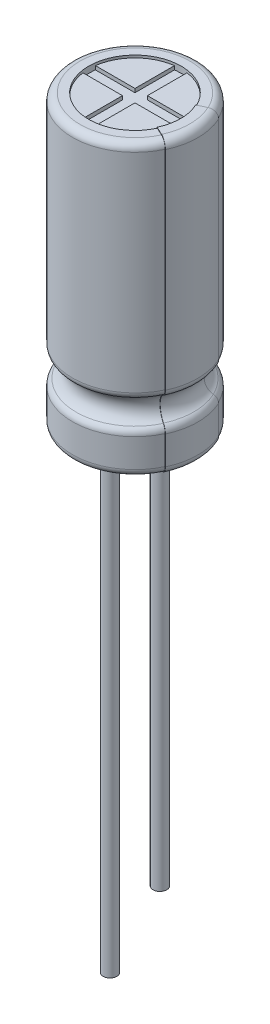
SolidWorks part; units mm, degrees
note: The reader was unsure of these and kept them because the rebuilt part matched: shared geometry of "Sketch7<4>".
ref_plane "Front Plane" through (0, 0, 0) normal (0, 0, 1) x (1, 0, 0)
ref_plane "Top Plane" through (0, 0, 0) normal (0, 1, 0) x (1, 0, 0)
ref_plane "Right Plane" through (0, 0, 0) normal (1, 0, 0) x (0, 0, -1)
sketch "Sketch1" plane through (0, 0, 0) normal (0, 0, 1) x (1, 0, 0)
  line L8 (0, 0.6) -> (1.9, 0.6)
  line L9 (1.9, 0.6) -> (1.9, 0.4)
  line L10 (1.9, 0.4) -> (2.2, 0.4)
  line L11 (2.5, 0.7) -> (2.5, 1.8415)
  line L12 (2.2, 12) -> (1.85, 12)
  line L13 (1.85, 12) -> (1.85, 11.75)
  line L14 (1.85, 11.75) -> (0, 11.75)
  line L15 (0, 11.75) -> (0, 0.6)
  line L16 (1.2518, 2.6) -> (5.492, 2.6) construction
  line L17 (2.5, 3.3585) -> (2.5, 11.7)
  arc A0 (2.2, 0.4) -> (2.5, 0.7) centre (2.2, 0.7) ccw
  arc A1 (2.5, 11.7) -> (2.2, 12) centre (2.2, 11.7) ccw
  arc A2 (2.3531, 3.1005) -> (2.3531, 2.0995) centre (2.65, 2.6) ccw
  arc A3 (2.5, 1.8415) -> (2.3531, 2.0995) centre (2.2, 1.8415) ccw
  arc A4 (2.5, 3.3585) -> (2.3531, 3.1005) centre (2.2, 3.3585) cw
  dimension "D8" = 0.3
  dimension "D11" = 1.1639
  dimension "D12" = 0.3
  dimension "D1" = 11.15
  dimension "D2" = 0.2
  dimension "D3" = 0.6
  dimension "D4" = 1.85
  dimension "D5" = 0.65
  dimension "D6" = 0.25
  dimension "D7" = 0.6
  dimension "D9" = 2.2
  dimension "D10" = 0.15
revolve "Revolve1" add sketch "Sketch1" angle 360 about L15
sketch "Sketch2" plane through (0, 11.75, 0) normal (0, 1, 0) x (1, 0, 0)
  line L0 (-0.25, 0.25) -> (-0.25, 1.833)
  line L2 (0.25, -1.833) -> (0.25, -0.25)
  line L4 (-0.25, -1.833) -> (-0.25, -0.25)
  line L5 (0.25, 0.25) -> (0.25, 1.833)
  line L7 (1.833, -0.25) -> (0.25, -0.25)
  line L9 (1.833, 0.25) -> (0.25, 0.25)
  line L13 (-0.25, -0.25) -> (-1.833, -0.25)
  line L16 (-0.25, 0.25) -> (-1.833, 0.25)
  arc A0 (0.25, -1.833) -> (1.833, -0.25) centre (0, 0) ccw
  arc A1 (1.833, 0.25) -> (0.25, 1.833) centre (0, 0) ccw
  arc A2 (-0.25, 1.833) -> (-1.833, 0.25) centre (0, 0) ccw
  arc A3 (-1.833, -0.25) -> (-0.25, -1.833) centre (0, 0) ccw
  dimension "D3" = 1.85
  dimension "D1" = 0.5
  dimension "D2" = 0.5
  dimension "D4" = 0.25
  dimension "D5" = 0.25
  dimension "D6" = 0.5
extrude "Boss-Extrude1" add sketch "Sketch2" along normal blind 0.15 separate body
sketch "Sketch3" plane through (0, 0.6, 0) normal (0, -1, 0) x (1, 0, 0)
  circle A0 centre (0, 0) radius 1.5
  ellipse E0 centre (0, 0) end of major axis (-1.4, 0) minor radius 0.8
  dimension "D1" = 3
extrude "Boss-Extrude2" add sketch "Sketch3" along normal blind 0.6 separate body
sketch "Sketch4" plane through (0, 0.6, 0) normal (0, -1, 0) x (1, 0, 0)
sketch "Sketch5" plane through (0, 0, 0) normal (0, 0, 1) x (1, 0, 0)
  line L8 (1.85, 12) -> (2.2, 12)
  line L10 (2.5, 3.3585) -> (2.5, 11.7) construction
  line L11 (2.5, 11.7) -> (2.5, 3.3585)
  line L12 (1.85, 12) -> (1.9, 0.4)
  line L13 (1.9, 0.4) -> (2.2, 0.4)
  line L14 (0, 0) -> (0, 15.0032) construction
  line L15 (2.52, 11.7) -> (2.52, 3.3585)
  line L16 (2.5, 0.7) -> (2.5, 1.8415)
  line L17 (2.52, 0.7) -> (2.52, 1.8415)
  line L18 (1.8801, 0.38) -> (2.2, 0.38)
  line L19 (1.8299, 12.02) -> (1.8801, 0.38)
  line L20 (1.8299, 12.02) -> (2.2, 12.02)
  arc A5 (2.2, 12) -> (2.5, 11.7) centre (2.2, 11.7) cw
  arc A6 (2.2, 0.4) -> (2.5, 0.7) centre (2.2, 0.7) ccw construction
  arc A7 (2.5, 1.8415) -> (2.3531, 2.0995) centre (2.2, 1.8415) ccw
  arc A8 (2.5, 3.3585) -> (2.3531, 3.1005) centre (2.2, 3.3585) cw
  arc A9 (2.3531, 3.1005) -> (2.3531, 2.0995) centre (2.65, 2.6) ccw
  arc A10 (2.5, 0.7) -> (2.2, 0.4) centre (2.2, 0.7) cw
  arc A11 (2.2, 12.02) -> (2.52, 11.7) centre (2.2, 11.7) cw
  arc A12 (2.52, 3.3585) -> (2.3633, 3.0833) centre (2.2, 3.3585) cw
  arc A13 (2.3633, 3.0833) -> (2.3633, 2.1167) centre (2.65, 2.6) ccw
  arc A14 (2.52, 1.8415) -> (2.3633, 2.1167) centre (2.2, 1.8415) ccw
  arc A15 (2.52, 0.7) -> (2.2, 0.38) centre (2.2, 0.7) cw
  dimension "D1" = 0.02
revolve "Revolve3" add sketch "Sketch5" angle 25 about L14
sketch "Sketch7" plane through (0, 0.6, 0) normal (0, -1, 0) x (1, 0, 0)
  line L0 (-1.4523, 0) -> (1.4342, 0) construction
  line L1 (0, 0) -> (0, 0.7626) construction
  circle A0 centre (-1, 0) radius 0.275
  circle A2 centre (1, 0) radius 0.275
  dimension "D2" = 0.55
  dimension "D1" = 1
extrude "Boss-Extrude3" add sketch "Sketch7" along normal blind 19.6 contours A0
extrude "Boss-Extrude4" add sketch "Sketch7<4>" along normal blind 15.6 contours A2
sketch "Sketch7<4>" plane through (0, 0.6, 0) normal (0, -1, 0) x (1, 0, 0) same geometry as "Sketch7"
